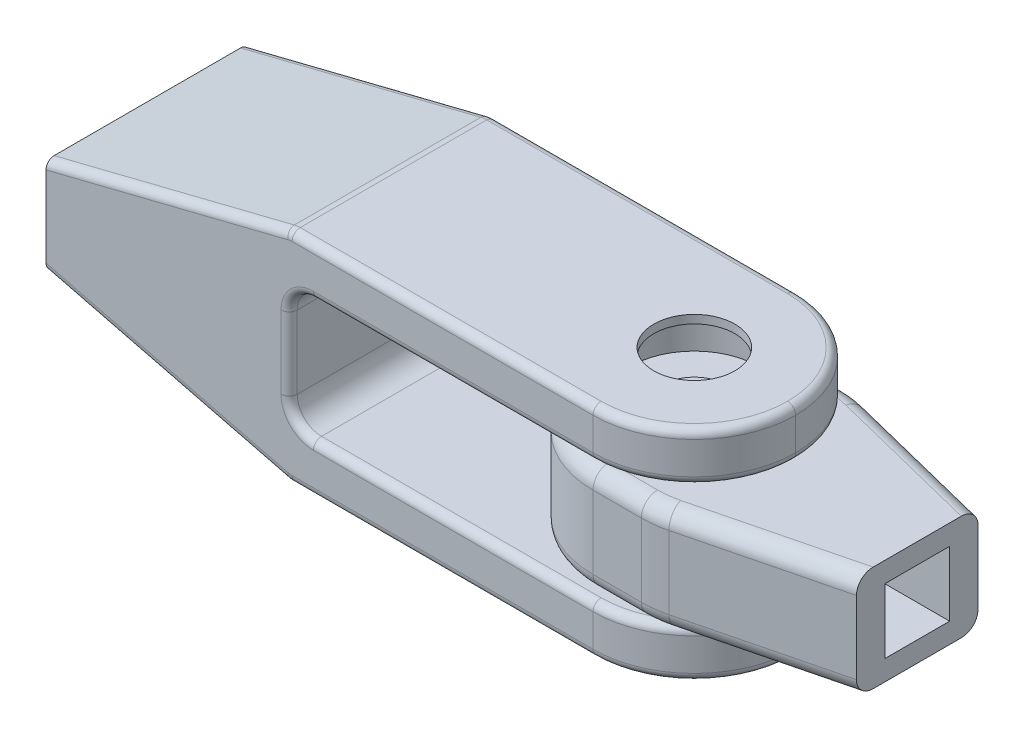
SolidWorks part; units mm, degrees
material "ABS"
ref_plane "Front Plane" through (0, 0, 0) normal (0, 0, 1) x (1, 0, 0)
ref_plane "Top Plane" through (0, 0, 0) normal (0, 1, 0) x (1, 0, 0)
ref_plane "Right Plane" through (0, 0, 0) normal (1, 0, 0) x (0, 0, -1)
sketch "Sketch1" plane through (0, 0, 0) normal (0, 0, 1) x (1, 0, 0)
  line L0 (0, 13.5) -> (50, 13.5)
  line L1 (50, 13.5) -> (50, 7.5)
  line L2 (50, 7.5) -> (0, 7.5)
  line L3 (0, 7.5) -> (0, -7.5)
  line L4 (0, -7.5) -> (50, -7.5)
  line L5 (50, -7.5) -> (50, -13.5)
  line L6 (50, -13.5) -> (0, -13.5)
  line L7 (0, -13.5) -> (-30, -6)
  line L8 (-30, -6) -> (-30, 6)
  line L9 (-30, 6) -> (0, 13.5)
  line L10 (-30, 0) -> (0, 0) construction
  dimension "D1" = 15
  dimension "D2" = 6
  dimension "D3" = 12
  dimension "D4" = 30
  dimension "D5" = 50
extrude "Boss-Extrude1" add sketch "Sketch1" along normal mid plane 25 contours L9 L0 L1 L2 L3 L4 L5 L6 L7 L8
fillet "Fillet1" radius 12.5 4 edges at (50, -10.5, -12.5) (50, -10.5, 12.5) (50, 10.5, -12.5) (50, 10.5, 12.5)
fillet "Fillet2" radius 3 4 edges at (0, -13.5, 0) (0, -7.5, 0) (0, 13.5, 0) (0, 7.5, 0)
sketch "Sketch2" plane through (-30, 0, 0) normal (-1, 0, 0) x (0, 0, 1)
  line L1 (4, -4) -> (-4, -4)
  line L2 (4, -4) -> (4, 4)
  line L3 (4, 4) -> (-4, 4)
  line L4 (-4, -4) -> (-4, 4)
  line L5 (4, -4) -> (-4, 4) construction
  line L6 (4, 4) -> (-4, -4) construction
  point P0 (0, 0)
  dimension "D1" = 8
extrude "Cut-Extrude1" cut sketch "Sketch2" against normal blind 20
sketch "Sketch3" plane through (0, 0, 0) normal (0, 1, 0) x (1, 0, 0)
  circle A0 centre (37.5, 0) radius 7.9375
  arc A1 (50, 0) -> (37.5, 12.5) centre (37.5, 0) ccw construction
  dimension "D1" = 15.875
extrude "Cut-Extrude2" cut sketch "Sketch3" against normal mid plane 24.9581
sketch "Sketch4" plane through (0, 0, 0) normal (0, 1, 0) x (1, 0, 0)
  circle A0 centre (37.5, 0) radius 5
  arc A1 (50, 0) -> (37.5, 12.5) centre (37.5, 0) ccw construction
  dimension "D1" = 10
extrude "Cut-Extrude3" cut sketch "Sketch4" against normal through all both and the other way through all
sketch "Sketch5" plane through (0, 0, 0) normal (0, 0, 1) x (1, 0, 0)
  line L0 (50, 13.5) -> (50, 7.5) construction
  line L1 (25, 6.5) -> (65, 6.5)
  line L2 (25, 6.5) -> (25, -6.5)
  line L3 (25, -6.5) -> (65, -6.5)
  line L4 (65, 6.5) -> (65, -6.5)
  line L5 (37.5, -6.5) -> (37.5, -7.5) construction
  line L6 (37.5, 7.5) -> (3, 7.5) construction
  line L7 (0, 0) -> (1, 0) construction
  line L8 (0, 4.5) -> (0, -4.5) construction
  line L9 (37.5, 7.5) -> (37.5, 6.5) construction
  dimension "D1" = 1
  dimension "D2" = 40
  dimension "D3" = 25
extrude "Boss-Extrude2" add sketch "Sketch5" along normal mid plane 25 separate body
fillet "Fillet4" radius 12.5 2 edges at (25, 0, 12.5) (25, 0, -12.5)
sketch "Sketch7" plane through (0, 6.5, 0) normal (0, 1, 0) x (1, 0, 0)
  line L0 (45, 12.5) -> (65, 7.5)
  line L1 (65, 12.5) -> (37.5, 12.5) construction
  line L2 (65, -12.5) -> (65, 12.5) construction
  line L3 (65, 7.5) -> (65, 12.5)
  line L4 (65, 12.5) -> (45, 12.5)
  line L5 (65, -7.5) -> (65, -12.5)
  line L6 (65, -12.5) -> (45, -12.5)
  line L7 (65, -12.5) -> (37.5, -12.5) construction
  line L8 (45, -12.5) -> (65, -7.5)
  circle A0 centre (37.5, 0) radius 2.5
  arc A1 (37.5, 12.5) -> (25, 0) centre (37.5, 0) ccw construction
  dimension "D1" = 5
  dimension "D2" = 15
  dimension "D3" = 20
extrude "Cut-Extrude4" cut sketch "Sketch7" against normal through all both and the other way through all
sketch "Sketch9" plane through (65, 0, 0) normal (1, 0, 0) x (0, 0, -1)
  line L1 (4, -4) -> (-4, -4)
  line L2 (4, -4) -> (4, 4)
  line L3 (4, 4) -> (-4, 4)
  line L4 (-4, -4) -> (-4, 4)
  line L5 (4, -4) -> (-4, 4) construction
  line L6 (4, 4) -> (-4, -4) construction
  point P0 (0, 0)
  dimension "D1" = 8
extrude "Cut-Extrude5" cut sketch "Sketch9" against normal blind 20
sketch "Sketch10" plane through (0, 0, 0) normal (0, -1, 0) x (1, 0, 0)
  circle A0 centre (37.5, 0) radius 4
  circle A1 centre (37.5, 0) radius 2.5
  circle A2 centre (37.5, 0) radius 2.5 construction
  dimension "D1" = 8
extrude "Boss-Extrude3" add sketch "Sketch10" along normal mid plane 15
fillet "Fillet5" radius 12.5 2 edges at (45, 0, 12.5) (45, 0, -12.5)
fillet "Fillet6" radius 2 16 edges at (55.7464, 6.5, 9.8134) (44.9885, 6.5, 12.4063) (40.4806, 6.5, 12.5) (28.6612, 6.5, 8.8388) (28.6612, 6.5, -8.8388) (40.4806, 6.5, -12.5) (44.9885, 6.5, -12.4063) (55.7464, -6.5, 9.8134) (44.9885, -6.5, 12.4063) (40.4806, -6.5, 12.5) (28.6612, -6.5, 8.8388) (28.6612, -6.5, -8.8388) (40.4806, -6.5, -12.5) (44.9885, -6.5, -12.4063) (55.7464, 6.5, -9.8134) (55.7464, -6.5, -9.8134)
fillet "Fillet3" radius 1 30 edges at (46.3388, 7.5, 8.8388) (46.3388, 7.5, -8.8388) (20.25, 7.5, -12.5) (0.8787, 6.6213, -12.5) (0, 0, -12.5) (0.8787, -6.6213, -12.5) (20.25, -7.5, -12.5) (46.3388, -7.5, -8.8388) (46.3388, -7.5, 8.8388) (20.25, -7.5, 12.5) (0.8787, -6.6213, 12.5) (0, 0, 12.5) (0.8787, 6.6213, 12.5) (-15.1791, -9.7052, -12.5) (0.0028, -13.4775, -12.5) (18.9347, -13.5, -12.5) (46.3388, -13.5, -8.8388) (46.3388, -13.5, 8.8388) (18.9347, -13.5, 12.5) (0.0028, -13.4775, 12.5) (-15.1791, 9.7052, -12.5) (0.0028, 13.4775, -12.5) (18.9347, 13.5, -12.5) (46.3388, 13.5, -8.8388) (46.3388, 13.5, 8.8388) (18.9347, 13.5, 12.5) (0.0028, 13.4775, 12.5) (20.25, 7.5, 12.5) (-15.1791, -9.7052, 12.5) (-15.1791, 9.7052, 12.5)
split "Split1" bodies to split 110 106 resulting bodies 111 112 split by face at (37.5, -13.5, 5)
